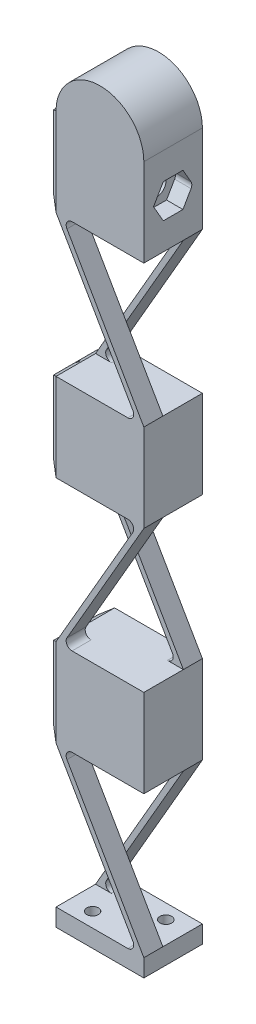
SolidWorks part; units mm, degrees
material "PET"
ref_plane "Front Plane" through (0, 0, 0) normal (0, 0, 1) x (1, 0, 0)
ref_plane "Top Plane" through (0, 0, 0) normal (0, 1, 0) x (1, 0, 0)
ref_plane "Right Plane" through (0, 0, 0) normal (1, 0, 0) x (0, 0, -1)
sketch "Sketch1" plane through (0, 0, 0) normal (0, 0, 1) x (1, 0, 0)
  line L0 (0, 0) -> (57.9688, 0) construction
  line L1 (7.5, 12.1244) -> (-7.5, 12.1244)
  line L2 (7.5, -27.1244) -> (-7.5, -27.1244)
  line L3 (7.5, -27.1244) -> (7.5, -12.1244)
  line L4 (7.5, -12.1244) -> (-7.5, -12.1244)
  line L5 (-7.5, -27.1244) -> (-7.5, -12.1244)
  line L6 (7.5, -27.1244) -> (-7.5, -12.1244) construction
  line L7 (7.5, -12.1244) -> (-7.5, -27.1244) construction
  line L8 (-7.5, 27.1244) -> (-7.5, 12.1244)
  line L9 (0, 0) -> (0, 41.5625) construction
  line L10 (7.5, 27.1244) -> (-7.5, 27.1244)
  line L11 (7.5, 27.1244) -> (7.5, 12.1244)
  line L12 (-7.5, 12.1244) -> (6.5, -12.1244)
  line L13 (6.5, -12.1244) -> (7.5, -12.1244)
  line L14 (7.5, -12.1244) -> (-6.5, 12.1244)
  line L15 (-6.5, 12.1244) -> (-7.5, 12.1244)
  line L16 (7.5, 12.1244) -> (-6.5, -12.1244)
  line L17 (-7.5, -12.1244) -> (6.5, 12.1244)
  point P1 (0, -19.6244)
  dimension "D1" = 15
  dimension "D2" = 60
extrude "Boss-Extrude1" add sketch "Sketch1" along normal mid plane 10 contours L5 L2 L3 L4 region at (0, -19.6244, 0)
extrude "Boss-Extrude2" add sketch "Sketch1<3>" against normal blind 3.25 from surface contours L17 L4 L16 L12 | L17 L14 L16 L1 | L17 L12 L16 L14 region at (3.6296, 6.276, 0) region at (0, 0, 0) region at (-3.6296, -6.276, 0) starting at face at (0, -19.6244, 5)
sketch "Sketch1<3>" plane through (0, 0, 0) normal (0, 0, 1) x (1, 0, 0) same geometry as "Sketch1"
extrude "Boss-Extrude3" add sketch "Sketch1<4>" along normal blind 3.25 from surface contours L12 L17 L14 L1 | L14 L16 L12 L4 | L17 L12 L16 L14 region at (0, 0, 0) region at (3.6296, -6.276, 0) region at (-3.6296, 6.276, 0) starting at face at (0, -19.6244, -5)
sketch "Sketch1<4>" plane through (0, 0, 0) normal (0, 0, 1) x (1, 0, 0) same geometry as "Sketch1"
extrude "Boss-Extrude4" add sketch "Sketch1<5>" along normal mid plane 10 contours L11 L10 L8 L1 region at (0, 19.6244, 0)
sketch "Sketch1<5>" plane through (0, 0, 0) normal (0, 0, 1) x (1, 0, 0) same geometry as "Sketch1"
ref_plane "Plane1" through (0, 19.6244, 0) normal (0, -1, 0) x (-1, 0, 0)
ref_plane "Plane2" through (7.5, -27.1244, 5) normal (-1, 0, 0) x (0, 0, 1)
ref_plane "Plane3" through (0, -19.6244, 0) normal (0, 1, 0) x (1, 0, 0)
mirror "Mirror2" about plane through (0, 19.6244, 0) normal (0, -1, 0) of "Boss-Extrude2", "Boss-Extrude3"
mirror "Mirror3" about plane through (0, 19.6244, 0) normal (0, -1, 0) of "Boss-Extrude1"
mirror "Mirror4" about plane through (0, -19.6244, 0) normal (0, 1, 0) of "Boss-Extrude2"
mirror "Mirror5" about plane through (0, -19.6244, 0) normal (0, 1, 0) of "Boss-Extrude3"
mirror "Mirror6" about plane through (0, -19.6244, 0) normal (0, 1, 0) of "Boss-Extrude4"
sketch "Sketch29" plane through (0, 0, 5) normal (0, 0, 1) x (1, 0, 0)
  line L0 (7.5, 66.3731) -> (-7.5, 66.3731) construction
  line L1 (7.5, 66.3731) -> (-7.5, 66.3731)
  arc A0 (-7.5, 66.3731) -> (7.5, 66.3731) centre (0, 66.3731) cw
  line M10 (7.5, 66.3731) -> (-7.5, 66.3731)
extrude "Boss-Extrude5" add sketch "Sketch29" against normal up to surface (10 mm away) contours A0 M10 region at (0, 69.5562, 5) up to face at (0, 0, -5)
ref_plane "Plane4" through (0, -54.3731, 0) normal (0, 1, 0) x (1, 0, 0)
sketch "Sketch36" plane through (0, -54.3731, 0) normal (0, 1, 0) x (1, 0, 0)
  line L4 (7.5, -5) -> (7.5, 5)
  line L5 (7.5, 5) -> (-7.5, 5)
  line L6 (-7.5, 5) -> (-7.5, -5)
  line L7 (-7.5, -5) -> (7.5, -5)
  line L8 (7.5, -5) -> (7.5, 5)
  line L9 (7.5, 5) -> (-7.5, 5)
  line L10 (-7.5, 5) -> (-7.5, -5)
  line L11 (-7.5, -5) -> (7.5, -5)
  dimension "D1" = 0
extrude "Cut-Extrude1" cut sketch "Sketch36" against normal through all
fillet "Fillet1" radius 1 12 edges at (-6.5, -12.1244, 3.375) (6.5, -12.1244, -3.375) (-6.5, 12.1244, -3.375) (6.5, 12.1244, 3.375) (6.5, 51.3731, -3.375) (-6.5, 51.3731, 3.375) (6.5, 27.1244, 3.375) (-6.5, 27.1244, -3.375) (-6.5, -51.3731, -3.375) (6.5, -51.3731, 3.375) (6.5, -27.1244, -3.375) (-6.5, -27.1244, 3.375)
sketch "Sketch48" plane through (0, -51.3731, 0) normal (0, 1, 0) x (1, 0, 0)
  line L0 (0, 0) -> (-7.5, -5) construction
  line L1 (-7.5, -5) -> (7.5, -5) construction
  line L2 (0, 0) -> (-3.3333, 5) construction
  line L3 (7.5, 5) -> (-7.5, 5) construction
  circle A0 centre (-3.75, -2.5) radius 1
  circle A1 centre (3.75, 2.5) radius 1
  point P6 (-3.75, -2.5)
  point P9 (3.75, 2.5)
  dimension "D1" = 2
hole_wizard "Ø2.0 mm Dowel Holes1" positions "Sketch48" profile "Sketch49" hole size "Ø2.0" standard "DIN" end condition through all
sketch "Sketch49" plane through (3.75, -51.3731, -2.5) normal (1, 0, 0) x (0, 0, 1)
  line L0 (0, 0) -> (0, 3)
  line L1 (0, 3) -> (1, 3)
  line L2 (1, 3) -> (1, 0)
  line L5 (1, 0) -> (0, 0)
  line L11 (0, -6.35) -> (0, 107.95) construction
  dimension "Thru Hole Dia." = 2
  dimension "Thru Hole Depth" = 3
ref_plane "Plane5" through (0, 0, 0) normal (0, 0, 1) x (1, 0, 0)
ref_plane "Plane6" through (-9.5, 0, 0) normal (-1, 0, 0) x (0, 0, 1)
sketch "Sketch82" plane through (-9.5, 0, 0) normal (-1, 0, 0) x (0, 0, 1)
  line L0 (-3.5, 64.8731) -> (-3.5, 52.8731)
  line L1 (-3.5, 52.8731) -> (1.75, 52.8731)
  line L2 (1.75, 52.8731) -> (3.5, 52.8731)
  line L3 (3.5, 52.8731) -> (3.5, 64.8731)
  line L4 (3.5, 64.8731) -> (-3.5, 64.8731)
  line L5 (-5, 66.3731) -> (-5, 51.3731)
  line L6 (-5, 51.3731) -> (1.75, 51.3731)
  line L7 (1.75, 51.3731) -> (5, 51.3731)
  line L8 (5, 51.3731) -> (5, 66.3731)
  line L9 (5, 66.3731) -> (-5, 66.3731)
  line L10 (-5, 66.3731) -> (-5, 51.3731)
  line L11 (-5, 51.3731) -> (1.75, 51.3731)
  line L12 (1.75, 51.3731) -> (5, 51.3731)
  line L13 (5, 51.3731) -> (5, 66.3731)
  line L14 (5, 66.3731) -> (-5, 66.3731)
  dimension "D2" = 1.5
loft "Loft1" add section face at (-7.5, 57.3731, 0.35) section "Sketch82" connector at (-7.5, 66.3731, 5) connector at (-9.5, 64.8731, 3.5)
sketch "Sketch83" plane through (-9.5, 0, 0) normal (-1, 0, 0) x (0, 0, 1)
  line L0 (-3.5, 25.6244) -> (-3.5, 13.6244)
  line L1 (-3.5, 13.6244) -> (-1.75, 13.6244)
  line L2 (-1.75, 13.6244) -> (3.5, 13.6244)
  line L3 (3.5, 13.6244) -> (3.5, 25.6244)
  line L4 (3.5, 25.6244) -> (-1.75, 25.6244)
  line L5 (-1.75, 25.6244) -> (-3.5, 25.6244)
  line L6 (-5, 27.1244) -> (-5, 12.1244)
  line L7 (-5, 12.1244) -> (-1.75, 12.1244)
  line L8 (-1.75, 12.1244) -> (5, 12.1244)
  line L9 (5, 12.1244) -> (5, 27.1244)
  line L10 (5, 27.1244) -> (-1.75, 27.1244)
  line L11 (-1.75, 27.1244) -> (-5, 27.1244)
  line L12 (-5, 27.1244) -> (-5, 12.1244)
  line L13 (-5, 12.1244) -> (-1.75, 12.1244)
  line L14 (-1.75, 12.1244) -> (5, 12.1244)
  line L15 (5, 12.1244) -> (5, 27.1244)
  line L16 (5, 27.1244) -> (-1.75, 27.1244)
  line L17 (-1.75, 27.1244) -> (-5, 27.1244)
  line L18 (-5, -12.1244) -> (-5, -27.1244)
  line L19 (-5, -27.1244) -> (1.75, -27.1244)
  line L20 (1.75, -27.1244) -> (5, -27.1244)
  line L21 (5, -27.1244) -> (5, -12.1244)
  line L22 (5, -12.1244) -> (1.75, -12.1244)
  line L23 (1.75, -12.1244) -> (-5, -12.1244)
  line L24 (-5, -12.1244) -> (-5, -27.1244)
  line L25 (-5, -27.1244) -> (1.75, -27.1244)
  line L26 (1.75, -27.1244) -> (5, -27.1244)
  line L27 (5, -27.1244) -> (5, -12.1244)
  line L28 (5, -12.1244) -> (1.75, -12.1244)
  line L29 (1.75, -12.1244) -> (-5, -12.1244)
  line L30 (-3.5, -13.6244) -> (-3.5, -25.6244)
  line L31 (-3.5, -25.6244) -> (1.75, -25.6244)
  line L32 (1.75, -25.6244) -> (3.5, -25.6244)
  line L33 (3.5, -25.6244) -> (3.5, -13.6244)
  line L34 (3.5, -13.6244) -> (1.75, -13.6244)
  line L35 (1.75, -13.6244) -> (-3.5, -13.6244)
  dimension "D3" = 1.5
  dimension "D4" = 1.5
loft "Loft2" add section face at (-7.5, 19.6244, -0.5833) section "Sketch83" connector at (-7.5, 27.1244, 5) connector at (-9.5, 25.6244, 3.5)
sketch "Sketch84" plane through (-9.5, 0, 0) normal (-1, 0, 0) x (0, 0, 1)
  line L0 (-3.5, -13.6244) -> (-3.5, -25.6244)
  line L1 (-3.5, -25.6244) -> (1.75, -25.6244)
  line L2 (1.75, -25.6244) -> (3.5, -25.6244)
  line L3 (3.5, -25.6244) -> (3.5, -13.6244)
  line L4 (3.5, -13.6244) -> (1.75, -13.6244)
  line L5 (1.75, -13.6244) -> (-3.5, -13.6244)
  line L6 (-5, -12.1244) -> (-5, -27.1244)
  line L7 (-5, -27.1244) -> (1.75, -27.1244)
  line L8 (1.75, -27.1244) -> (5, -27.1244)
  line L9 (5, -27.1244) -> (5, -12.1244)
  line L10 (5, -12.1244) -> (1.75, -12.1244)
  line L11 (1.75, -12.1244) -> (-5, -12.1244)
  line L12 (-5, -12.1244) -> (-5, -27.1244)
  line L13 (-5, -27.1244) -> (1.75, -27.1244)
  line L14 (1.75, -27.1244) -> (5, -27.1244)
  line L15 (5, -27.1244) -> (5, -12.1244)
  line L16 (5, -12.1244) -> (1.75, -12.1244)
  line L17 (1.75, -12.1244) -> (-5, -12.1244)
  dimension "D2" = 1.5
loft "Loft3" add section face at (-7.5, -19.6244, 0.5833) section "Sketch84" connector at (-7.5, -12.1244, 5) connector at (-9.5, -13.6244, 3.5)
sketch "Sketch97" plane through (7.5, 0, 0) normal (1, 0, 0) x (0, 0, -1)
  line L0 (-5, 66.3731) -> (5, 51.3731) construction
  line L1 (5, 66.3731) -> (-5, 51.3731) construction
  line L2 (-5, 66.3731) -> (5, 66.3731) construction
  line L3 (-1.6743, 61.7731) -> (-3.3486, 58.8731)
  line L4 (-3.3486, 58.8731) -> (-1.6743, 55.9731)
  line L5 (-1.6743, 55.9731) -> (1.6743, 55.9731)
  line L6 (1.6743, 55.9731) -> (3.3486, 58.8731)
  line L7 (3.3486, 58.8731) -> (1.6743, 61.7731)
  line L8 (1.6743, 61.7731) -> (-1.6743, 61.7731)
  circle A0 centre (0, 58.8731) radius 2.9 construction
  point P8 (0, 58.8731)
  dimension "D1" = 5.8
extrude "Cut-Extrude4" cut sketch "Sketch97" against normal blind 2.8
sketch "Sketch98" plane through (4.7, 0, 0) normal (1, 0, 0) x (0, 0, -1)
  line L0 (-1.6743, 61.7731) -> (1.6743, 55.9731) construction
  line L1 (1.6743, 61.7731) -> (-1.6743, 55.9731) construction
  circle A0 centre (0, 58.8731) radius 1.6
  point P8 (0, 58.8731)
  dimension "D1" = 3.2
extrude "Cut-Extrude5" cut sketch "Sketch98" against normal blind 8
sketch "Sketch99" plane through (0, 0, 0) normal (0, 0, 1) x (1, 0, 0)
  line L0 (7.5, 66.3731) -> (7.5, 51.3731) construction
  line L1 (-9.5, 52.8731) -> (-9.5, 64.8731) construction
  line L2 (7.5, 66.3731) -> (7.5, 51.3731) construction
  line L3 (-9.5, 52.8731) -> (-9.5, 64.8731) construction
  line L4 (-7.5, -54.3731) -> (7.5, -54.3731) construction
  line L5 (-7.5, -54.3731) -> (7.5, -54.3731) construction
  line L6 (7.5, 58.8731) -> (-5.75, 58.8731)
  line L7 (-8.75, 55.8731) -> (-8.75, -54.3731)
  arc A0 (-5.75, 58.8731) -> (-8.75, 55.8731) centre (-5.75, 55.8731) ccw
  point P8 (0, 0)
  dimension "D2" = 3
  dimension "D1" = 1.5
sweep "Cut-Sweep5" cut path "Sketch99" circular profile diameter 0.5 parameters "D3"=0.5
fillet "Fillet5" radius 1 1 edges at (-3.3, 59.1231, 0)
fillet "Fillet6" radius 1 19 edges at (-7.5, 66.3731, 0) (6.1, 58.8731, -3.3486)
equation "\"a\"= 3.25"
equation "\"D1@Boss-Extrude2\"=\"a\""
equation "\"D1@Boss-Extrude3\"= \"a\""
equation "\"d_sheath\"= 3.5'M2 threaded inserts"
equation "\"r\"= 3.2'radius for tendon routing"
equation "\"angle\"= 60deg'angle of cross flexures"
equation "\"side_length\"= 15mm"
equation "\"d\"= \"side_length\" + \"d1\"'for linear patterns"
equation "\"w\"= 1mm'width of the cross flexures"
equation "\"d1\"= tan ( \"angle\" ) * \"diff\"'dist between top face and bottom face of 2 consecutive fingers"
equation "\"diff\"= \"side_length\" - \"w\""
equation "\"D3@Sketch1\"=\"w\""
equation "\"D2@Sketch1\"=\"angle\""
equation "\"offset\"= 1.5'loft offset for finger surface"
equation "\"D2@Sketch82\"=\"offset\""
equation "\"D3@Sketch83\"=\"offset\""
equation "\"D4@Sketch83\"=\"offset\""
equation "\"D2@Sketch84\"=\"offset\""
